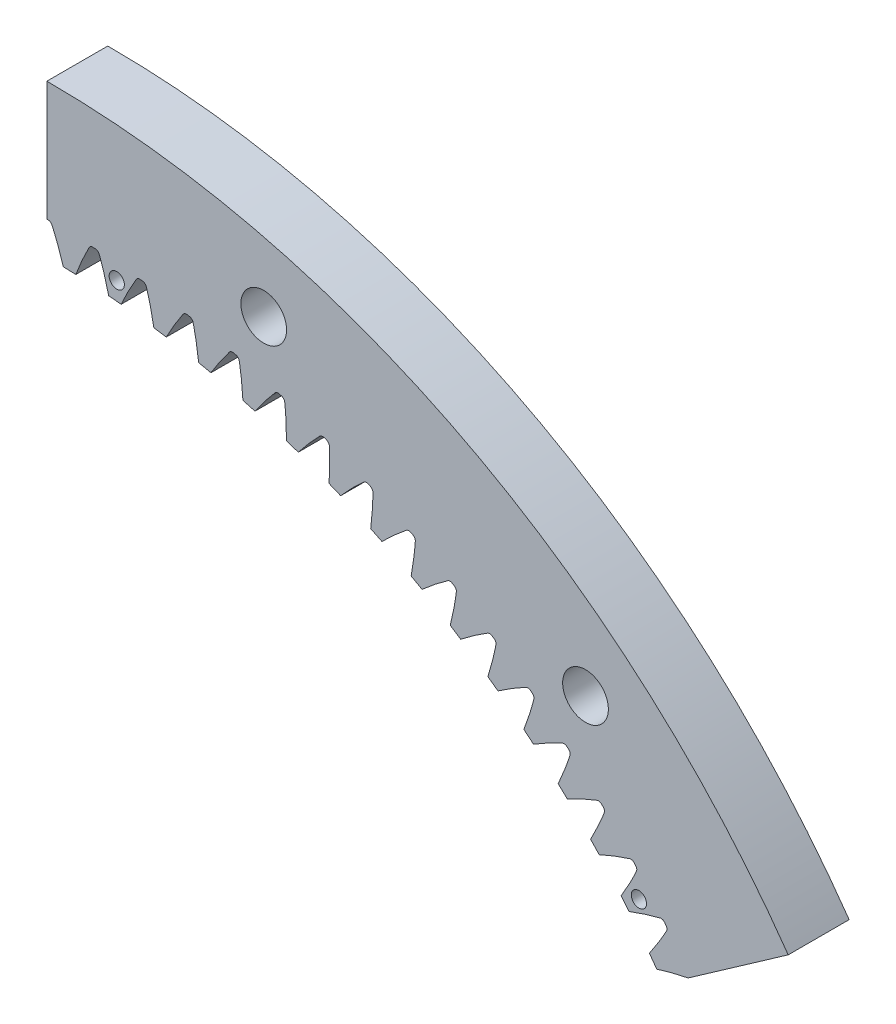
SolidWorks part; units mm, degrees
material "Д16 ГОСТ 4784-97"
ref_plane "FRONT" through (0, 0, 0) normal (0, 0, 1) x (1, 0, 0)
ref_plane "TOP" through (0, 0, 0) normal (0, 1, 0) x (1, 0, 0)
ref_plane "RIGHT" through (0, 0, 0) normal (1, 0, 0) x (0, 0, -1)
ref_axis "Ось1" through (0, 0, 50) along (0, 0, -1)
sketch "SketchRevolveSpurAssemblyNew2Gear" plane through (0, 0, 0) normal (1, 0, 0) x (0, 0, -1)
  line L0 (0, 0) -> (1, 0) construction
  line L1 (0, 49.399) -> (0, 59.399)
  line L2 (0, 59.399) -> (4, 59.399)
  line L3 (4, 59.399) -> (4, 49.399)
  line L4 (4, 49.399) -> (0, 49.399)
  dimension "MinorDiameter" = 49.399
  dimension "D1" = 4
  dimension "D2" = 10
revolve "SpurAssemblyNew2Gear" add sketch "SketchRevolveSpurAssemblyNew2Gear" angle 360 about L0
sketch "SketchToothSpurAssemblyNew2Gear" plane through (0, 0, 0) normal (0, 0, 1) x (1, 0, 0)
  arc A0 (49.1395, -1.1537) -> (49.1395, 1.1537) centre (0, 0) ccw
  spline S0 degree 3 poles (49.1395, 1.1537) (49.2861, 1.1124) (49.5102, 1.0454) (49.8138, 0.9473) (50.0554, 0.8652) (50.306, 0.7758) (50.5651, 0.6788) (50.8329, 0.5746) (51.108, 0.4599) (51.3094, 0.3804) (51.4272, 0.3224) (51.4611, 0.2973) (51.4911, 0.268) (51.5164, 0.2347) (51.5367, 0.198) (51.5565, 0.1461) (51.5633, 0.0916) (51.5623, 0.0385) (51.5626, 0) (51.5623, -0.0385) (51.5633, -0.0916) (51.5565, -0.1461) (51.5367, -0.198) (51.5164, -0.2347) (51.4911, -0.268) (51.4611, -0.2973) (51.4272, -0.3224) (51.3094, -0.3804) (51.108, -0.4599) (50.8329, -0.5746) (50.5651, -0.6788) (50.306, -0.7758) (50.0554, -0.8652) (49.8138, -0.9473) (49.5102, -1.0454) (49.2861, -1.1124) (49.1395, -1.1537) knots 0 0 0 0 0.081489 0.125094 0.170606 0.218025 0.26735 0.318583 0.371722 0.426768 0.434365 0.441808 0.449251 0.456695 0.464138 0.471581 0.486277 0.493139 0.5 0.506861 0.513723 0.528419 0.535862 0.543305 0.550749 0.558192 0.565635 0.573232 0.628278 0.681417 0.73265 0.781975 0.829394 0.874906 0.918511 1 1 1 1
extrude "ToothExtrudeCutSpurAssemblyNew2Gear" cut sketch "SketchToothSpurAssemblyNew2Gear" against normal blind 4 and the other way blind 4
pattern_circular "PatternSpurAssemblyNew2Gear" count 104 every 3.462 about axis through (0, 0, 50) along (0, 0, -1) of "ToothExtrudeCutSpurAssemblyNew2Gear"
sketch "AuxiliarySketchSpurAssemblyNew2Gear" plane through (0, 0, 0) normal (0, 0, 1) x (1, 0, 0)
  circle A0 centre (0, 0) radius 50 construction
  circle A1 centre (0, 0) radius 46.9846 construction
  circle A2 centre (0, 0) radius 51.5625 construction
  circle A3 centre (0, 0) radius 49.399 construction
  dimension "PitchDiameter" = 100
  dimension "BaseDiameter" = 93.9693
  dimension "MajorDiameter" = 103.125
  dimension "MinorDiameter" = 98.7981
sketch "Эскиз1" plane through (0, 0, 0) normal (0, 0, 1) x (1, 0, 0)
  line L0 (0, 0) -> (0, 72.3035)
  line L1 (0, 0) -> (59.2276, 41.4716)
  line L2 (0, 0) -> (16.8075, 62.7263) construction
  line L3 (0, 0) -> (51.5096, 61.3868) construction
  arc A0 (0, 72.3035) -> (59.2276, 41.4716) centre (0, 0) ccw
  circle A1 centre (0, 0) radius 55 construction
  circle A2 centre (14.235, 53.1259) radius 1.5
  circle A3 centre (35.3533, 42.1324) radius 1.5
  dimension "D2" = 15
  dimension "D3" = 110
  dimension "D4" = 3
  dimension "D6" = 3
  dimension "D1" = 55
  dimension "D5" = 25
extrude "Вырез-Вытянуть1" cut sketch "Эскиз1" against normal through all
sketch "Эскиз2" plane through (0, 0, 0) normal (0, 0, 1) x (1, 0, 0)
  circle A0 centre (38.8569, 32.329) radius 0.5
  circle A1 centre (4.5893, 50.3751) radius 0.5
extrude "Вырез-Вытянуть2" cut sketch "Эскиз2" against normal blind 1
